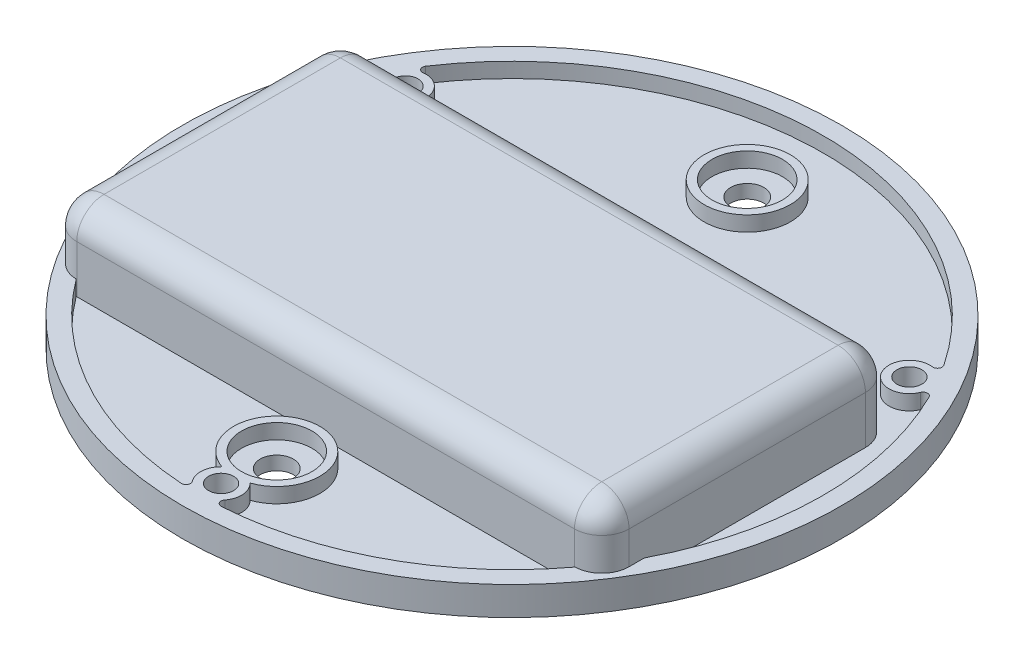
SolidWorks part; units mm, degrees
ref_plane "Plan de face" through (0, 0, 0) normal (0, 0, 1) x (1, 0, 0)
ref_plane "Plan de dessus" through (0, 0, 0) normal (0, 1, 0) x (1, 0, 0)
ref_plane "Plan de droite" through (0, 0, 0) normal (1, 0, 0) x (0, 0, -1)
sketch "Esquisse1" plane through (0, 0, 0) normal (0, 0, 1) x (1, 0, 0)
  line L0 (0, 0) -> (0, 36.7399) construction
  line L1 (0, 0) -> (-72.5, 0)
  line L2 (-72.5, 0) -> (-72.5, 6.3)
  line L3 (-72.5, 6.3) -> (-68.5, 6.3)
  line L4 (-68.5, 6.3) -> (-68.5, 3)
  line L5 (-68.5, 3) -> (0, 3)
  line L6 (0, 0) -> (0, 3)
  dimension "D1" = 6.3
  dimension "D2" = 3.3
  dimension "D3" = 145
  dimension "D4" = 137
revolve "Révolution1" add sketch "Esquisse1" angle 360 about L0
sketch "Esquisse2" plane through (0, 3, 0) normal (0, 1, 0) x (1, 0, 0)
  line L1 (-60.75, -41) -> (60.75, -41)
  line L2 (-60.75, -41) -> (-60.75, 23)
  line L3 (-60.75, 23) -> (60.75, 23)
  line L4 (60.75, -41) -> (60.75, 23)
  dimension "D1" = 64
  dimension "D2" = 121.5
  dimension "D3" = 60.75
  dimension "D4" = 41
extrude "Boss.-Extru.1" add sketch "Esquisse2" along normal blind 16.5
fillet "Congé1" radius 6 8 edges at (0, 19.5, -23) (60.75, 19.5, 9) (0, 19.5, 41) (-60.75, 19.5, 9) (60.75, 11.25, 41) (60.75, 11.25, -23) (-60.75, 11.25, -23) (-60.75, 11.25, 41)
sketch "Esquisse3" plane through (0, 6.3, 0) normal (0, 1, 0) x (1, 0, 0)
  line L0 (0, 0) -> (37.7485, 0) construction
  arc A0 (-3.0937, -60.7321) -> (3.0937, -60.7321) centre (0, -64) ccw
  arc A1 (-54.8758, -40.9987) -> (54.8758, -40.9987) centre (0, 0) ccw construction
  circle A2 centre (0, -51.75) radius 7.75
  arc A3 (3.0937, -60.7321) -> (-3.0937, -60.7321) centre (0, -51.75) ccw
  circle A4 centre (-55.4256, 32) radius 4.5
  circle A5 centre (55.4256, 32) radius 4.5
  circle A6 centre (0, 51.75) radius 9.5
  circle A7 centre (0, 51.75) radius 7.75
  dimension "D1" = 9
  dimension "D2" = 15.5
  dimension "D3" = 19
  dimension "D4" = 3
extrude "Boss.-Extru.4" add sketch "Esquisse3" against normal up to surface (3.3 mm away) separate body up to face at (0, 3, -19.8893)
sketch "Esquisse4" plane through (0, 6.3, 0) normal (0, 1, 0) x (1, 0, 0)
  arc A1 (-54.8758, -40.9987) -> (54.8758, -40.9987) centre (0, 0) ccw construction
  arc A3 (-4.4194, -68.3573) -> (4.4194, -68.3573) centre (0, 0) ccw
  arc A4 (4.4194, -68.3573) -> (3.563, -66.7486) centre (4.3548, -67.3594) cw
  arc A5 (-3.0937, -60.7321) -> (3.0937, -60.7321) centre (0, -64) ccw construction
  arc A6 (-3.563, -66.7486) -> (3.563, -66.7486) centre (0, -64) ccw
  arc A7 (-3.563, -66.7486) -> (-4.4194, -68.3573) centre (-4.3548, -67.3594) cw
  arc A8 (-56.0244, 36.46) -> (-56.9895, 38.0059) centre (-56.1575, 37.4511) cw
  arc A9 (-56.0244, 36.46) -> (-59.5875, 30.2886) centre (-55.4256, 32) ccw
  arc A10 (-56.9895, 38.0059) -> (-61.4088, 30.3514) centre (0, 0) ccw
  arc A11 (-61.4088, 30.3514) -> (-59.5875, 30.2886) centre (-60.5123, 29.9083) cw
  arc A12 (59.5875, 30.2886) -> (61.4088, 30.3514) centre (60.5123, 29.9083) cw
  arc A13 (59.5875, 30.2886) -> (56.0244, 36.46) centre (55.4256, 32) ccw
  arc A14 (61.4088, 30.3514) -> (56.9895, 38.0059) centre (0, 0) ccw
  arc A15 (56.9895, 38.0059) -> (56.0244, 36.46) centre (56.1575, 37.4511) cw
  arc M3 (-3.0937, -60.7321) -> (3.0937, -60.7321) centre (0, -64) ccw
  dimension "D1" = 1
  dimension "D2" = 1
  dimension "D3" = 3
extrude "Boss.-Extru.5" add sketch "Esquisse4" against normal up to surface (3.3 mm away) contours A8 A10 A9 | A10 A11 A9 | A14 A15 A13 | A12 A14 A13 | A7 A3 M3 | A3 A4 M3 region at (-2.7055, 6.3, 68.0506) region at (2.7055, 6.3, 68.0506) region at (-57.5808, 6.3, -36.3683) region at (-60.2863, 6.3, -31.6823) region at (60.2863, 6.3, -31.6823) region at (57.5808, 6.3, -36.3683) up to face at (0, 3, -19.8893)
sketch "Esquisse5" plane through (0, 3, 0) normal (0, 1, 0) x (1, 0, 0)
  circle A0 centre (0, -51.75) radius 3.65
  circle A1 centre (0, 51.75) radius 3.65
  dimension "D1" = 7.3
  dimension "D2" = 7.3
extrude "Enlèv. mat.-Extru.1" cut sketch "Esquisse5" against normal blind 10
hole_wizard "Fraisage pour vis à tête fraisée M51" positions "Esquisse7" profile "Esquisse6" countersink size "M5" standard "ISO" end condition through all
sketch "Esquisse7" plane through (0, 0, 0) normal (0, -1, 0) x (1, 0, 0)
  point P0 (0, 64)
  point P1 (55.4256, -32)
  point P3 (-55.4256, -32)
sketch "Esquisse6" plane through (0, 0, 64) normal (1, 0, 0) x (0, 0, -1)
  line L0 (0, 0) -> (0, 19.5)
  line L1 (0, 19.5) -> (2.75, 19.5)
  line L2 (2.75, 19.5) -> (2.75, 2.45)
  line L3 (2.75, 2.45) -> (5.2, 0)
  line L5 (5.2, 0) -> (0, 0)
  line L6 (-2.75, 2.45) -> (-5.2, 0) construction
  line L11 (0, -6.35) -> (0, 107.95) construction
  dimension "Diamètre du perçage jusqu'au prochain" = 5.5
  dimension "Profondeur du perçage jusqu'au prochain" = 19.5
  dimension "Diamètre du fraisage entrant" = 10.4
  dimension "Angle du fraisage entrant" = 90
sketch "Esquisse8" plane through (0, 0, 0) normal (0, -1, 0) x (1, 0, 0)
  circle A0 centre (-46, -42.5) radius 6
  circle A1 centre (46, -42.5) radius 6
  circle A2 centre (10.9538, 61.6647) radius 6
  circle A3 centre (0, 64) radius 5.2 construction
  dimension "D1" = 12
  dimension "D2" = 12
  dimension "D6" = 12
  dimension "D3" = 92
  dimension "D4" = 46
  dimension "D5" = 42.5
  dimension "D7" = 62.63
extrude "Boss.-Extru.6" add sketch "Esquisse8" along normal blind 3.5 draft 14
